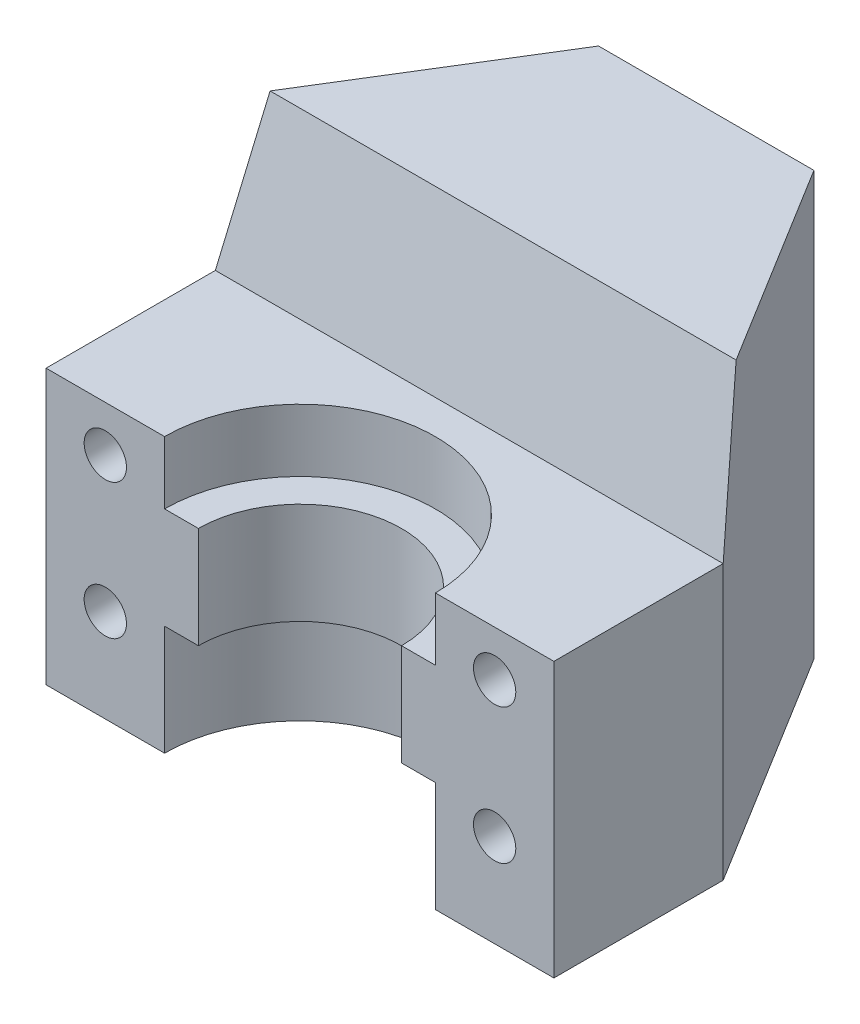
SolidWorks part; units mm, degrees
material "PLA"
ref_plane "Front Plane" through (0, 0, 0) normal (0, 0, 1) x (1, 0, 0)
ref_plane "Top Plane" through (0, 0, 0) normal (0, 1, 0) x (1, 0, 0)
ref_plane "Right Plane" through (0, 0, 0) normal (1, 0, 0) x (0, 0, -1)
sketch "Sketch1" plane through (0, 0, 0) normal (1, 0, 0) x (0, 0, -1)
  line L0 (0, 20) -> (12, 20) construction
  line L1 (0, 0) -> (12, 0)
  line L2 (0, 0) -> (0, 25)
  line L3 (0, 25) -> (12, 25)
  line L4 (12, 0) -> (12, 25)
  line L5 (0, 5) -> (12, 5) construction
  dimension "D1" = 15
  dimension "D2" = 12
  dimension "D3" = 25
  dimension "D4" = 5
extrude "Boss-Extrude1" add sketch "Sketch1" along normal mid plane 30 contours L4 L3 L2 L1
sketch "Sketch2" plane through (0, 0, 0) normal (0, 1, 0) x (1, 0, 0)
  line L0 (0, 0) -> (0, -2) construction
  line L1 (-15, -12) -> (15, -12)
  line L2 (-15, -12) -> (-15, -2)
  line L3 (-15, -2) -> (15, -2)
  line L4 (15, -12) -> (15, -2)
  line L5 (15, 0) -> (15, 12) construction
  dimension "D1" = 2
  dimension "D3" = 10
extrude "Boss-Extrude2" add sketch "Sketch2" along normal blind 16.2 separate body
sketch "Sketch3" plane through (15, 0, 0) normal (1, 0, 0) x (0, 0, -1)
  line L1 (-2, 0) -> (-2, 16.2) construction
  line L7 (0, 25) -> (0, 0) construction
  line L9 (-2, 0) -> (-2, 16.2)
  line L15 (0, 25) -> (0, 0)
  line L16 (0, 25) -> (-2, 16.2)
  line L17 (-2, 0) -> (0, 0)
extrude "Boss-Extrude3" add sketch "Sketch3" against normal up to surface (30 mm away) up to face at (-15, 8.1, 7)
hole_wizard "M5x0.8 Tapped Hole1" positions "Sketch7" profile "Sketch6" tap size "M5x0.8" standard "ANSI Metric"
sketch "Sketch7" plane through (0, 0, -12) normal (0, 0, -1) x (-1, 0, 0)
  line L0 (-15, 0) -> (15, 0) construction
  point P0 (0, 20)
  point P2 (0, 5)
  dimension "D1" = 15
  dimension "D2" = 5
sketch "Sketch6" plane through (0, 20, -12) normal (1, 0, 0) x (0, 1, 0)
  line L0 (0, 0) -> (0, 8.2618)
  line L1 (0, 8.2618) -> (2.1, 7)
  line L2 (2.1, 7) -> (2.1, 0)
  line L5 (2.1, 0) -> (0, 0)
  line L10 (0, 8.2618) -> (-2.1, 7) construction
  line L11 (0, -6.35) -> (0, 107.95) construction
  dimension "Tap Drill Dia." = 4.2
  dimension "Tap Drill Depth" = 7
  dimension "Drill Angle" = 118
cosmetic thread "Hole Thread1" parameters "D1"=4.2, "D2"=5
cosmetic thread "Hole Thread2" parameters "D1"=4.2, "D2"=5
sketch "Sketch9" plane through (0, 0, 0) normal (1, 0, 0) x (0, 0, -1)
  line L0 (-12, 16.2) -> (-4, 16.2)
  line L1 (-12, 16.2) -> (-12, 0) construction
  line L2 (-4, 16.2) -> (-4, 12.5)
  line L3 (-4, 12.5) -> (-6, 12.5)
  line L4 (-6, 12.5) -> (-6, 6.5)
  line L5 (-6, 6.5) -> (-4, 6.5)
  line L6 (-4, 6.5) -> (-4, 0)
  line L7 (-12, 0) -> (12, 0) construction
  line L8 (-4, 0) -> (-12, 0)
  line L9 (-12, 0) -> (-12, 16.2)
  line L10 (-12, 16.2) -> (-2, 16.2) construction
  dimension "D1" = 6
  dimension "D2" = 8
  dimension "D3" = 8
  dimension "D4" = 6.5
  dimension "D5" = 6
revolve "Cut-Revolve1" cut sketch "Sketch9" angle 360 about L9
sketch "Sketch10" plane through (0, 25, 0) normal (0, 1, 0) x (1, 0, 0)
  line L5 (15, -2) -> (15, 0) construction
  line L6 (-15, -2) -> (-6.3625, 12)
  line L7 (15, 12) -> (-15, 12) construction
  line L8 (-6.3625, 12) -> (-15, 12)
  line L9 (-15, 12) -> (-15, -2)
  line L10 (15, 12) -> (6.3625, 12)
  line L11 (15, -2) -> (15, 0)
  line L12 (6.3625, 12) -> (15, -2)
  line L13 (15, 12) -> (15, -2)
  line L14 (0, 0) -> (0, 12) construction
  line L15 (15, 0) -> (-15, 0) construction
  point P16 (0, 0)
  line M4 (-15, 12) -> (-15, 0)
  line M5 (-15, 0) -> (15, 0)
  line M6 (15, 0) -> (15, 12)
  line M7 (15, 12) -> (-15, 12)
  dimension "D1" = 12.725
extrude "Cut-Extrude2" cut sketch "Sketch10" against normal up to next contours L12 M7 M5 M6 | L12 L11 M5 | L6 M5 M7 M4 | L9 L6 M5 region at (-14.5887, 25, 0.6667) region at (-12.0694, 25, -7.5) region at (14.5887, 25, 0.6667) region at (12.0694, 25, -7.5)
hole_wizard "M3x0.5 Tapped Hole1" positions "Sketch12" profile "Sketch11" tap size "M3x0.5" standard "ANSI Metric"
sketch "Sketch12" plane through (0, 0, 12) normal (0, 0, 1) x (1, 0, 0)
  line L0 (0, 0) -> (0, 16.2) construction
  line L1 (8, 16.2) -> (-8, 16.2) construction
  line L4 (-11.5, 13.5) -> (-11.5, 5.5) construction
  line L7 (-11.5, 9.5) -> (0, 9.5) construction
  line L10 (-6, 6.5) -> (-6, 12.5) construction
  point P0 (-11.5, 13.5)
  point P2 (11.5, 13.5)
  point P7 (-11.5, 5.5)
  point P8 (11.5, 5.5)
  point P36 (-6, 9.5)
  dimension "D1" = 8
  dimension "D2" = 23
sketch "Sketch11" plane through (-11.5, 13.5, 12) normal (1, 0, 0) x (0, -1, 0)
  line L0 (0, 0) -> (0, 9.2511)
  line L1 (0, 9.2511) -> (1.25, 8.5)
  line L2 (1.25, 8.5) -> (1.25, 0)
  line L5 (1.25, 0) -> (0, 0)
  line L10 (0, 9.2511) -> (-1.25, 8.5) construction
  line L11 (0, -6.35) -> (0, 107.95) construction
  dimension "Tap Drill Dia." = 2.5
  dimension "Tap Drill Depth" = 8.5
  dimension "Drill Angle" = 118
cosmetic thread "Hole Thread3" parameters "D1"=6, "D2"=3
cosmetic thread "Hole Thread4" parameters "D1"=6, "D2"=3
cosmetic thread "Hole Thread5" parameters "D1"=6, "D2"=3
cosmetic thread "Hole Thread6" parameters "D1"=6, "D2"=3
